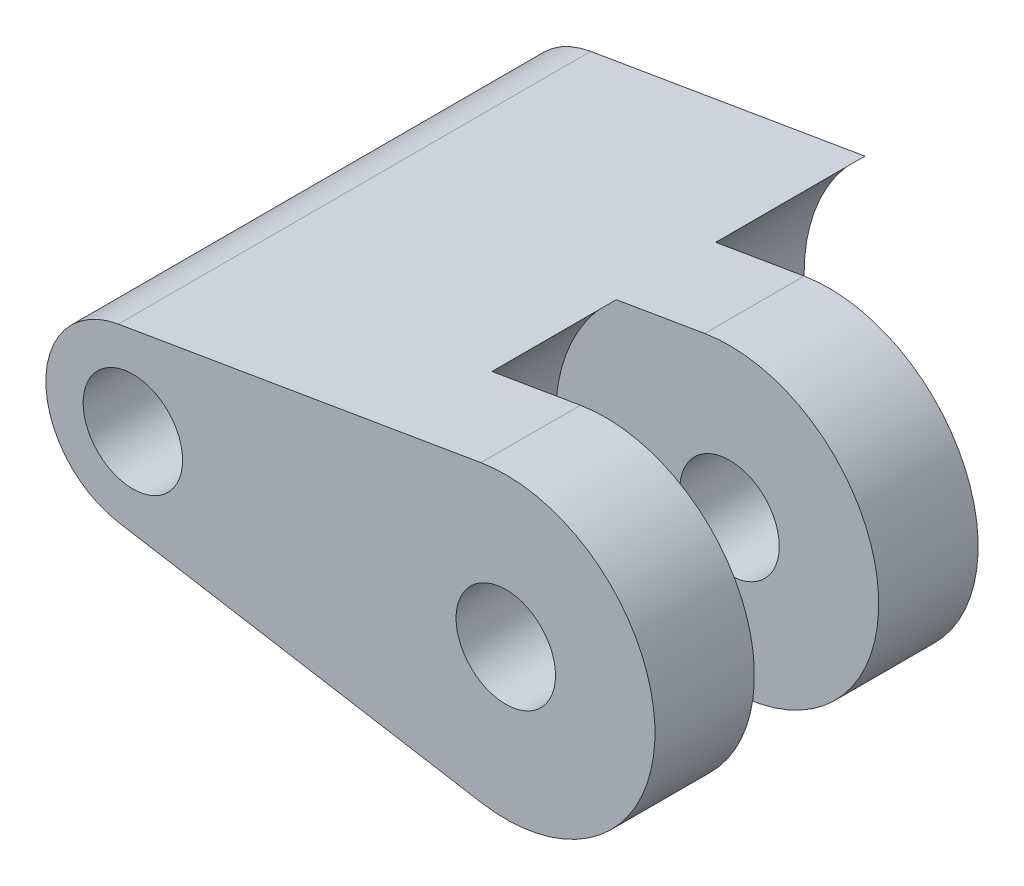
SolidWorks part; units mm, degrees
ref_plane "Plan de face" through (0, 0, 0) normal (0, 0, 1) x (1, 0, 0)
ref_plane "Plan de dessus" through (0, 0, 0) normal (0, 1, 0) x (1, 0, 0)
ref_plane "Plan de droite" through (0, 0, 0) normal (1, 0, 0) x (0, 0, -1)
sketch "Esquisse1" plane through (0, 0, 0) normal (0, 0, 1) x (1, 0, 0)
  line L0 (-0.5833, 3.451) -> (14, 5.9161)
  line L1 (-0.5833, -3.451) -> (14, -5.9161)
  circle A0 centre (0, 0) radius 2
  circle A2 centre (15, 0) radius 2
  circle A3 centre (15, 0) radius 6
  circle A4 centre (0, 0) radius 3.5
  circle A5 centre (15, 0) radius 7
  point P12 (0, 0)
  point P13 (13.6172, 5.8385)
  point P14 (14.299, -5.9589)
  dimension "D2" = 4
  dimension "D3" = 7
  dimension "D4" = 4
  dimension "D5" = 12
  dimension "D6" = 14
  dimension "D1" = 15
extrude "Boss.-Extru.2" add sketch "Esquisse1" along normal blind 19 contours A4 A0 | A5 L0 A4 L1 region at (5.7219, 0, 0) region at (2.1953, 2.5976, 0)
extrude "Boss.-Extru.3" add sketch "Esquisse1<4>" along normal blind 4 from offset 6 contours L0 A5 L1 A3 | A3 A2 region at (12.2446, 5.4848, 0) region at (18.7634, 4.453, 0)
sketch "Esquisse1<4>" plane through (0, 0, 0) normal (0, 0, 1) x (1, 0, 0) same geometry as "Esquisse1"
extrude "Boss.-Extru.4" add sketch "Esquisse1<5>" along normal blind 4 from offset 15 contours L0 A5 L1 A3 | A3 A2 region at (12.2446, 5.4848, 0) region at (18.7634, 4.453, 0)
sketch "Esquisse1<5>" plane through (0, 0, 0) normal (0, 0, 1) x (1, 0, 0) same geometry as "Esquisse1"
